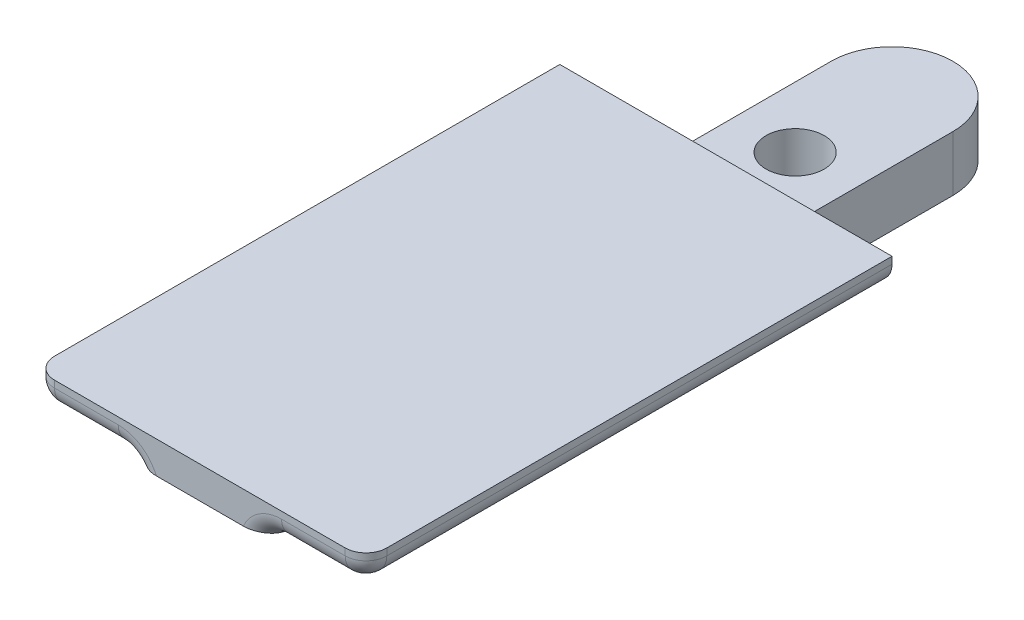
SolidWorks part; units mm, degrees
ref_plane "Front Plane" through (0, 0, 0) normal (0, 0, 1) x (1, 0, 0)
ref_plane "Top Plane" through (0, 0, 0) normal (0, 1, 0) x (1, 0, 0)
ref_plane "Right Plane" through (0, 0, 0) normal (1, 0, 0) x (0, 0, -1)
sketch "Sketch2" plane through (0, 0, 0) normal (0, 1, 0) x (1, 0, 0)
  line L0 (0, 0) -> (0, 12) construction
  line L1 (-4.4, 0) -> (-4.4, 12)
  line L2 (4.4, 0) -> (4.4, 12)
  line L8 (-4.4, 0) -> (-4.4, -38)
  line L9 (-4.4, -38) -> (4.4, -38)
  line L10 (4.4, -38) -> (4.4, 0)
  arc A1 (4.4, 12) -> (-4.4, 12) centre (0, 12) ccw
  circle A2 centre (0, 5) radius 2.1
  point P3 (0, 6)
  dimension "D1" = 4.4
  dimension "D4" = 4.2
  dimension "D2" = 12
  dimension "D3" = 5
  dimension "D5" = 38
extrude "Boss-Extrude1" add sketch "Sketch2" along normal blind 4
sketch "Sketch3" plane through (0, 4, 0) normal (0, 1, 0) x (1, 0, 0)
  line L1 (-12, 0) -> (12, 0)
  line L2 (-12, 0) -> (-12, -38)
  line L3 (-12, -38) -> (12, -38)
  line L4 (12, 0) -> (12, -38)
  circle A0 centre (0, 5) radius 2.1 construction
  dimension "D1" = 5
  dimension "D2" = 12
  dimension "D3" = 12
  dimension "D4" = 38
extrude "Boss-Extrude2" add sketch "Sketch3" along normal blind 2
chamfer "Chamfer1" distance 30 angle 7 1 edges at (0, 0, 38) first distance on face at (0, 0, 11.9)
fillet "Fillet2" radius 1.5 4 edges at (-12, 4, 19) (12, 4, 19) (-4.4, 4, 19) (4.4, 4, 19)
fillet "Fillet4" radius 1.5 8 edges at (5.4128, 3.9187, 38) (8.2, 4, 38) (11.5607, 4.4393, 38) (-5.4128, 3.9187, 38) (-8.2, 4, 38) (-11.5607, 4.4393, 38) (12, 5.75, 38) (-12, 5.75, 38)
